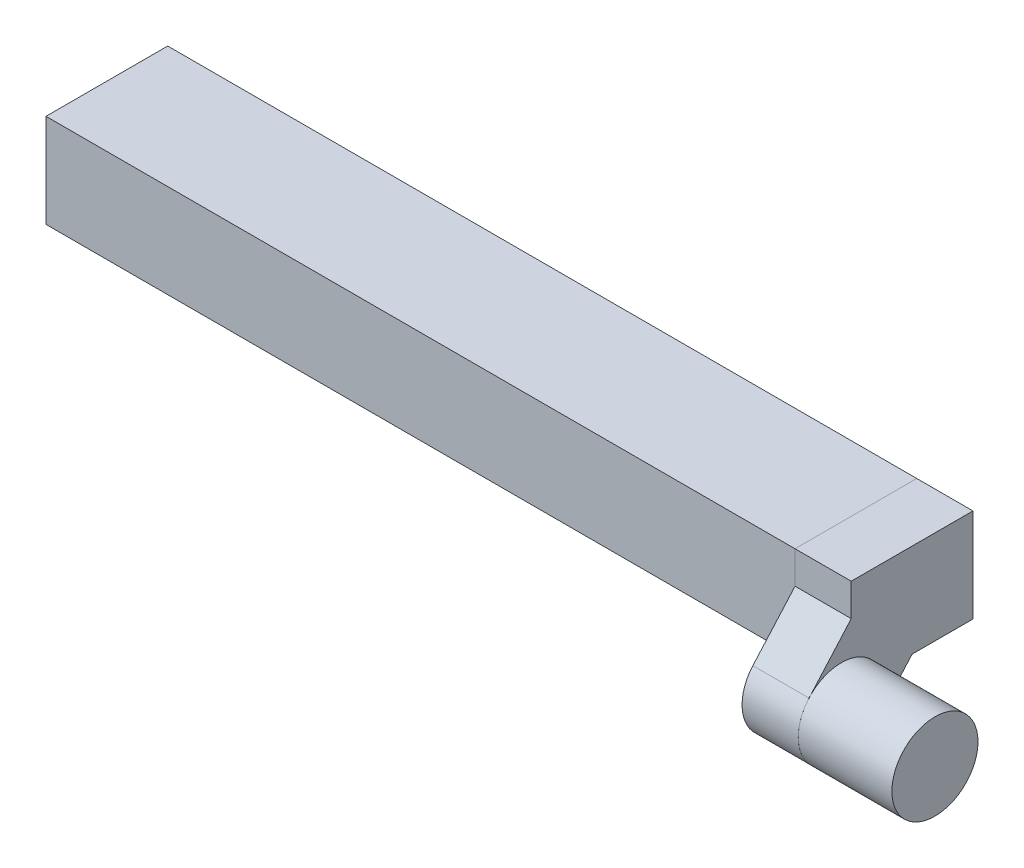
SolidWorks part; units mm, degrees
ref_plane "Front Plane" through (0, 0, 0) normal (0, 0, 1) x (1, 0, 0)
ref_plane "Top Plane" through (0, 0, 0) normal (0, 1, 0) x (1, 0, 0)
ref_plane "Right Plane" through (0, 0, 0) normal (1, 0, 0) x (0, 0, -1)
sketch "Sketch2" plane through (0, 0, 0) normal (1, 0, 0) x (0, 0, -1)
  line L1 (-2.05, -2.05) -> (2.05, -2.05)
  line L2 (-2.05, -2.05) -> (-2.05, 2.05)
  line L3 (-2.05, 2.05) -> (2.05, 2.05)
  line L4 (2.05, -2.05) -> (2.05, 2.05)
  line L5 (-2.05, -2.05) -> (2.05, 2.05) construction
  line L6 (-2.05, 2.05) -> (2.05, -2.05) construction
  line L7 (3.25, -2.5) -> (-3.25, -2.5)
  line L8 (3.25, -2.5) -> (3.25, 2.5)
  line L9 (3.25, 2.5) -> (-3.25, 2.5)
  line L10 (-3.25, -2.5) -> (-3.25, 2.5)
  line L11 (3.25, -2.5) -> (-3.25, 2.5) construction
  line L12 (3.25, 2.5) -> (-3.25, -2.5) construction
  point P0 (0, 0)
  point P5 (0, 0)
  dimension "D1" = 4.1
  dimension "D2" = 4.1
  dimension "D3" = 6.5
  dimension "D4" = 5
extrude "Boss-Extrude1" add sketch "Sketch2" along normal blind 10
extrude "Boss-Extrude2" add sketch "Sketch2<2>" along normal blind 25 from offset 15 contours L1 L4 L3 L2 | L10 L7 L8 L9 L4 L1 L2 L3 region at (0, 0, 0) region at (0, -2.418, 0)
sketch "Sketch2<2>" plane through (0, 0, 0) normal (1, 0, 0) x (0, 0, -1) same geometry as "Sketch2"
sketch "Sketch5" plane through (40, 0, 0) normal (1, 0, 0) x (0, 0, -1)
  line L0 (-0.02, -0.4959) -> (-4.75, -0.4959) construction
  line L6 (-3.25, 2.5) -> (3.25, 2.5)
  line L7 (3.25, 2.5) -> (3.25, -2.5)
  line L8 (3.25, -2.5) -> (0, -2.5)
  line L9 (-3.25, -2.5) -> (3.25, -2.5) construction
  line L10 (0, -2.5) -> (-2.0577, -4.8267)
  line L11 (-5.5035, -1.7793) -> (-3.25, 0.7688)
  line L12 (-3.25, -2.5) -> (-3.25, 2.5) construction
  line L13 (-5.5035, -1.7793) -> (-2.0577, -4.8267) construction
  line L14 (-3.25, 0.7688) -> (-3.25, 2.5)
  arc A1 (-5.5035, -1.7793) -> (-2.0577, -4.8267) centre (-3.7806, -3.303) ccw
  dimension "D1" = 4.73
  dimension "D3" = 5
  dimension "D4" = 4.6
extrude "Boss-Extrude3" add sketch "Sketch5" along normal blind 3
sketch "Sketch6" plane through (43, 0, 0) normal (1, 0, 0) x (0, 0, -1)
  circle A1 centre (-3.7806, -3.303) radius 2.3
  dimension "D1" = 4.6
extrude "Boss-Extrude4" add sketch "Sketch6" along normal blind 5
extrude "Boss-Extrude5" add sketch "Sketch2<4>" along normal blind 5 from offset 10
sketch "Sketch2<4>" plane through (0, 0, 0) normal (1, 0, 0) x (0, 0, -1) same geometry as "Sketch2"
